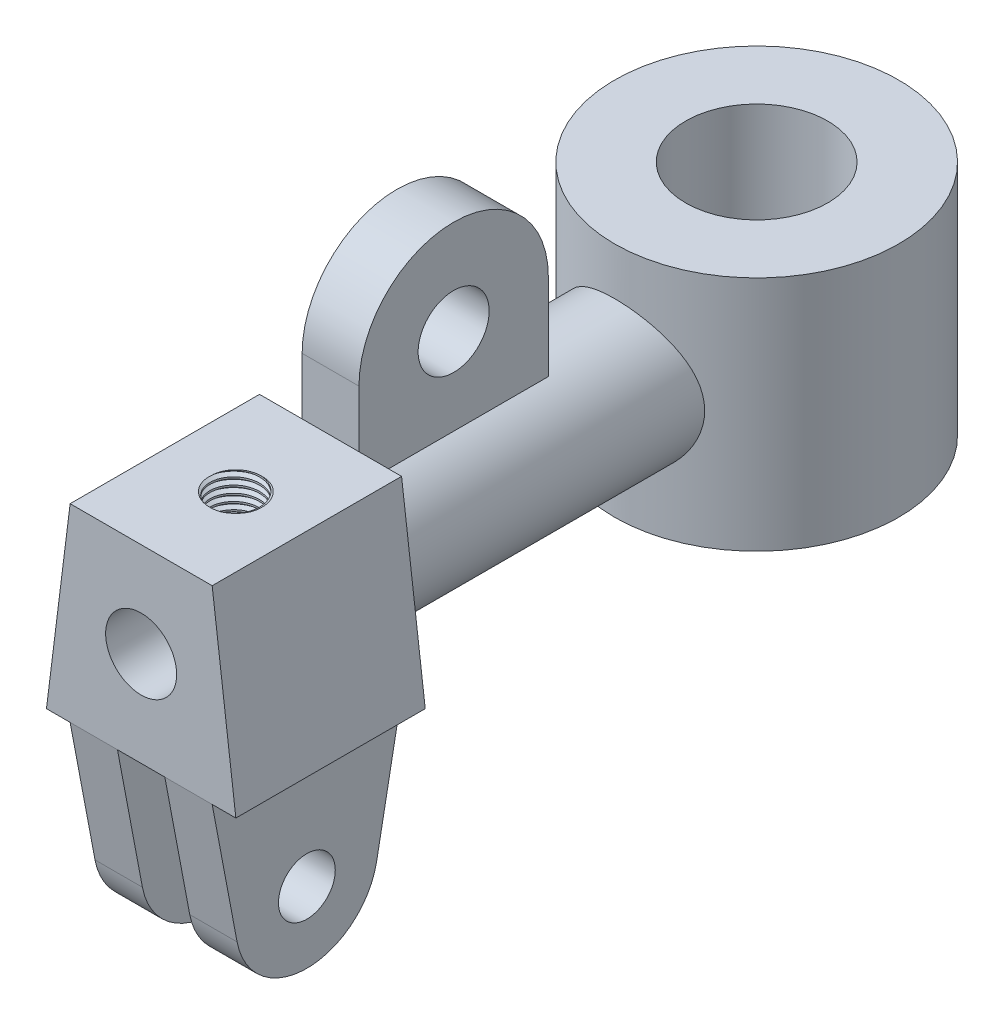
SolidWorks part; units mm, degrees
ref_plane "Front Plane" through (0, 0, 0) normal (0, 0, 1) x (1, 0, 0)
ref_plane "Top Plane" through (0, 0, 0) normal (0, 1, 0) x (1, 0, 0)
ref_plane "Right Plane" through (0, 0, 0) normal (1, 0, 0) x (0, 0, -1)
sketch "Sketch1" plane through (0, 0, 0) normal (0, 1, 0) x (1, 0, 0)
  circle A0 centre (0, 0) radius 30
  circle A1 centre (0, 0) radius 15
  dimension "D1" = 60
  dimension "D2" = 30
extrude "Boss-Extrude1" add sketch "Sketch1" along normal mid plane 50
ref_plane "Plane1" through (0, 0, 130) normal (0, 0, 1) x (1, 0, 0)
sketch "Sketch2" plane through (0, 0, 130) normal (0, 0, 1) x (1, 0, 0)
  line L0 (0, 0) -> (0, 50000) construction
  line L1 (0, 0) -> (50000, 0) construction
  line L2 (-20, -20) -> (20, -20)
  line L3 (20, -20) -> (15, 20)
  line L4 (15, 20) -> (-15, 20)
  line L5 (-15, 20) -> (-20, -20)
  circle A0 centre (0, 0) radius 15
  point P10 (0, -20)
  dimension "D1" = 30
  dimension "D2" = 30
  dimension "D3" = 40
  dimension "D4" = 40
  dimension "D5" = 20
extrude "Boss-Extrude2" add sketch "Sketch2" against normal blind 40 separate body
extrude "Boss-Extrude3" add sketch "Sketch2<3>" against normal up to next contours A0 region at (0, 0, 130)
sketch "Sketch2<3>" plane through (0, 0, 130) normal (0, 0, 1) x (1, 0, 0) same geometry as "Sketch2"
sketch "Sketch3" plane through (0, 0, 130) normal (0, 0, 1) x (1, 0, 0)
  circle A0 centre (0, 0) radius 7.5
  dimension "D1" = 15
extrude "Cut-Extrude1" cut sketch "Sketch3" against normal up to next
sketch "Sketch5" plane through (0, 0, 0) normal (1, 0, 0) x (0, 0, -1)
  line L0 (-90, -20) -> (-95.2619, -47.7905)
  line L1 (-124.7381, -47.7905) -> (-130, -20)
  line L2 (-90, -20) -> (-130, -20) construction
  line L3 (-130, -20) -> (-90, -20)
  arc A0 (-95.2619, -47.7905) -> (-124.7381, -47.7905) centre (-110, -45) cw
  circle A1 centre (-110, -45) radius 6
  point P9 (-110, -20)
  dimension "D1" = 25
  dimension "D2" = 15
  dimension "D3" = 12
extrude "Boss-Extrude5" add sketch "Sketch5" along normal blind 10 from offset 5
mirror "Mirror1" about plane through (0, 0, 0) normal (1, 0, 0) of "Boss-Extrude5"
sketch "Sketch6" plane through (0, 20, 0) normal (0, 1, 0) x (1, 0, 0)
  line L0 (15, -90) -> (-15, -90) construction
  line L1 (-6, -90) -> (6, -90)
  line L2 (-6, -90) -> (-6, -50)
  line L3 (-6, -50) -> (6, -50)
  line L4 (6, -90) -> (6, -50)
  line L5 (0, 0) -> (0, -50000) construction
  dimension "D1" = 40
  dimension "D2" = 12
extrude "Boss-Extrude6" add sketch "Sketch6" along normal blind 32 and the other way up to next
fillet "Fillet1" 2 edges at (0, 52, 90) (0, 52, 50) type full round first side face at (0, 36, 90) second side face at (0, 33.1869, 50) middle face at (0, 52, 70)
hole_wizard "Ø6.0mm Dowel Hole1" positions "Sketch7" profile "Sketch8" hole size "Ø6.0" standard "ANSI Metric" end condition through all
sketch "Sketch7" plane through (6, 0, 0) normal (1, 0, 0) x (0, 0, -1)
  point P0 (-70, 32)
sketch "Sketch8" plane through (6, 32, 70) normal (0, 1, 0) x (0, 0, -1)
  line L0 (0, 0) -> (0, 36)
  line L1 (0, 36) -> (7.5, 36)
  line L2 (7.5, 36) -> (7.5, 0)
  line L5 (7.5, 0) -> (0, 0)
  line L11 (0, -6.35) -> (0, 107.95) construction
  dimension "Thru Hole Dia." = 15
  dimension "Thru Hole Depth" = 36
hole_wizard "M12x1.5 Tapped Hole1" positions "Sketch9" profile "Sketch10" tap size "M12x1.5" standard "ANSI Metric" end condition up to next
sketch "Sketch9" plane through (0, 20, 0) normal (0, 1, 0) x (1, 0, 0)
  line L0 (15, -130) -> (-15, -130) construction
  point P0 (0, -110)
  dimension "D1" = 20
sketch "Sketch10" plane through (0, 20, 110) normal (1, 0, 0) x (0, 0, 1)
  line L0 (0, 0) -> (0, 12.5)
  line L1 (0, 12.5) -> (5.25, 12.5)
  line L2 (5.25, 12.5) -> (5.25, 0)
  line L5 (5.25, 0) -> (0, 0)
  line L11 (0, -6.35) -> (0, 107.95) construction
  dimension "Thru Tap Drill Dia." = 10.5
  dimension "Thru Tap Drill Depth" = 12.5
cosmetic thread "Hole Thread1" parameters "D2"=12
thread "Thread3" pitch 1.5 method cut profile "Thread Profile3" start angle 0, offset 1.5, length 20, pitch 1.5, diameter 10.5
ref_plane "Plane4" through (-5.25, 21.5, 110) normal (0, 0, 1) x (-1, 0, 0)
sketch "Thread Profile3" plane through (-5.25, 21.5, 110) normal (0, 0, 1) x (-1, 0, 0)
  line L0 (0, 0) -> (0, 1.5) construction
  line L1 (0, 0) -> (0.8119, 0.4687)
  line L2 (0.8119, 0.4687) -> (0.8119, 0.6562)
  line L3 (0.8119, 0.6562) -> (0, 1.125)
  line L4 (0.8119, 0.5625) -> (0, 0.5625) construction
  line L11 (0, 0) -> (0, 1.125)
  point P2 (0, 0)
  dimension "Pitch" = 1.5
  dimension "Profile_Angle" = 60
  dimension "Profile_Land" = 0.1875
  dimension "Profile_Height" = 0.8119
